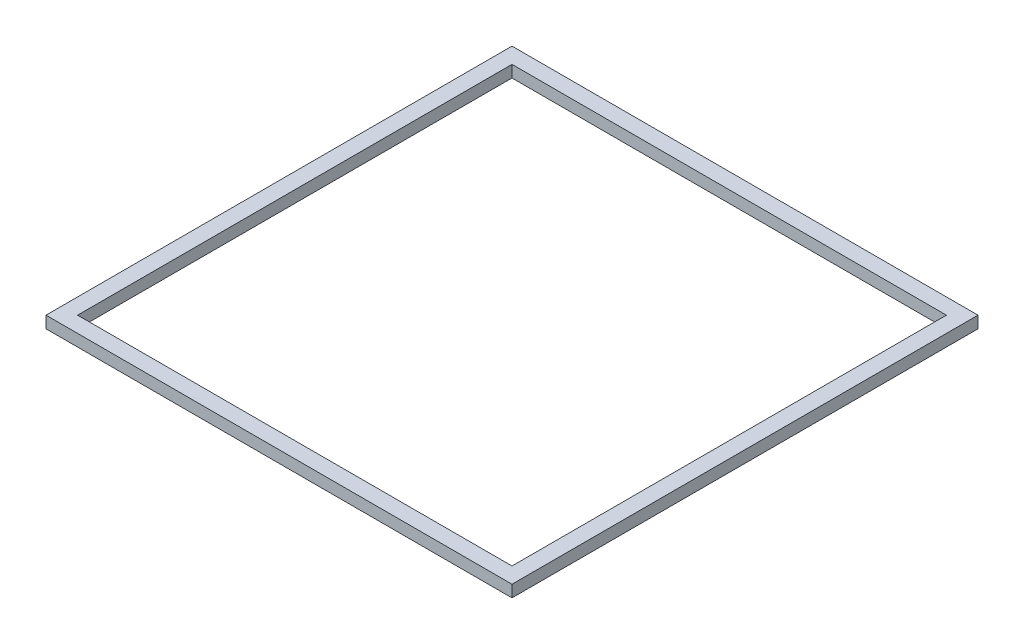
SolidWorks part; units mm, degrees
material "Concreto"
ref_plane "Plano frontal" through (0, 0, 0) normal (0, 0, 1) x (1, 0, 0)
ref_plane "Plano superior" through (0, 0, 0) normal (0, 1, 0) x (1, 0, 0)
ref_plane "Plano direito" through (0, 0, 0) normal (1, 0, 0) x (0, 0, -1)
sketch "Esboço1" plane through (0, 0, 0) normal (0, 1, 0) x (1, 0, 0)
  line L5 (-2750, 2750) -> (2750, 2750)
  line L6 (-2750, 2750) -> (-2750, -2750)
  line L11 (-2750, -2750) -> (2750, -2750)
  line L12 (2750, 2750) -> (2750, -2750)
  line L13 (-2750, 2750) -> (2750, -2750) construction
  line L14 (-2750, -2750) -> (2750, 2750) construction
  line L15 (-2950, 2950) -> (2950, 2950)
  line L16 (-2950, 2950) -> (-2950, -2950)
  line L17 (-2950, -2950) -> (2950, -2950)
  line L18 (2950, 2950) -> (2950, -2950)
  line L19 (-2950, 2950) -> (2950, -2950) construction
  line L20 (-2950, -2950) -> (2950, 2950) construction
  point P0 (0, 0)
  point P6 (0, 0)
  dimension "D1" = 5500
  dimension "D2" = 5500
  dimension "D3" = 200
  dimension "D4" = 200
extrude "Ressalto-extrusão1" add sketch "Esboço1" along normal blind 150
sketch "Esboço2" plane through (0, 150, 0) normal (0, 1, 0) x (1, 0, 0)
  line L0 (-2950, 0) -> (2950, 0) construction
  line L1 (-2950, 2950) -> (-2950, -2950) construction
  line L2 (2950, -2950) -> (2950, 2950) construction
  line L3 (0, 2950) -> (0, -2950) construction
  line L4 (2950, 2950) -> (-2950, 2950) construction
  line L5 (-2950, -2950) -> (2950, -2950) construction
  line L6 (-2950, 2950) -> (-2750, 2750) construction
  line L7 (2950, 2950) -> (2750, 2750) construction
  line L8 (2950, -2950) -> (2750, -2750) construction
  line L9 (-2950, -2950) -> (-2750, -2750) construction
  line L10 (-2850, 2850) -> (2850, 2850) construction
  line L11 (-2750, 2750) -> (-2750, 0) construction
  line L12 (-2850, -2850) -> (2850, -2850) construction
  line L13 (-2750, 2750) -> (-2750, -2750) construction
  line L14 (-2750, 0) -> (-2750, -2750) construction
  line L15 (2750, 2750) -> (2750, 0) construction
  line L16 (2750, -2750) -> (2750, 2750) construction
  line L17 (2750, 0) -> (2750, -2750) construction
  line L18 (-2750, 2750) -> (0, 2750) construction
  line L19 (2750, 2750) -> (-2750, 2750) construction
  line L20 (0, 2750) -> (2750, 2750) construction
  point P32 (-2750, -1375)
  point P36 (-2750, 1375)
  point P40 (2750, -1375)
  point P41 (2750, 1375)
  point P42 (1375, 2750)
  point P46 (-1375, 2750)
ref_plane "Plano1" through (0, 0, -2850) normal (0, 0, 1) x (1, 0, 0)
sketch "Esboço4" plane through (0, 0, -2850) normal (0, 0, 1) x (1, 0, 0)
  line L0 (-2850, 150) -> (2850, 150) construction
  line L1 (-2850, 150) -> (2850, 150) construction
  line L2 (2850, 150) -> (2850, 2850) construction
  line L3 (-2850, 150) -> (-2850, 3250) construction
  line L4 (2850, 2850) -> (-2850, 2850) construction
  line L6 (-2850, 3250) -> (2850, 2850) construction
  line L7 (0, 3050) -> (-14.0351, 2850) construction
  line L8 (2850, 2250) -> (-2850, 2250) construction
  line L9 (2850, 2250) -> (2250, 2850) construction
  line L10 (-2850, 2250) -> (-1915.5738, 3184.4262) construction
  dimension "D1" = 2700
  dimension "D2" = 3100
  dimension "D3" = 2100
  dimension "D4" = 45
  dimension "D5" = 45
